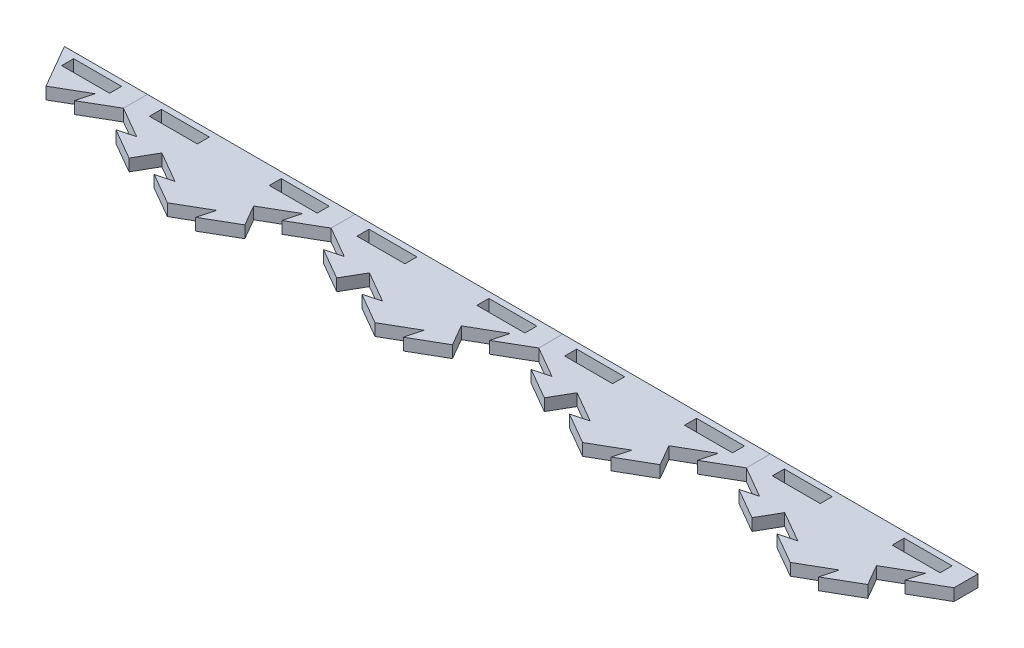
SolidWorks part; units mm, degrees
material "Cedar"
ref_plane "Front Plane" through (0, 0, 0) normal (0, 0, 1) x (1, 0, 0)
ref_plane "Top Plane" through (0, 0, 0) normal (0, 1, 0) x (1, 0, 0)
ref_plane "Right Plane" through (0, 0, 0) normal (1, 0, 0) x (0, 0, -1)
sketch "Sketch1" plane through (0, 0, 0) normal (0, 1, 0) x (1, 0, 0)
  line L0 (-54.9926, 0) -> (54.9926, 0) construction
  line L1 (-54.9926, 0) -> (0, -31.75)
  line L2 (0, -31.75) -> (54.9926, 0)
  line L3 (54.9926, 0) -> (54.9926, 63.5)
  line L4 (54.9926, 63.5) -> (0, 95.25)
  line L5 (0, 95.25) -> (-54.9926, 63.5)
  line L6 (-54.9926, 63.5) -> (-54.9926, 0)
  line L7 (0, -31.75) -> (0, 31.75) construction
  circle A0 centre (0, 31.75) radius 54.9926 construction
  point P9 (0, 0)
  dimension "D1" = 63.5
extrude "Boss-Extrude1" add sketch "Sketch1" against normal blind 6.35
sketch "Sketch2" plane through (0, 0, 0) normal (0, 1, 0) x (1, 0, 0)
  line L0 (-54.9926, 31.75) -> (54.9926, 31.75) construction
  line L1 (-54.9926, 63.5) -> (-54.9926, 0) construction
  line L2 (54.9926, 0) -> (54.9926, 63.5) construction
  point P2 (0, 31.75)
ref_axis "Axis1" through (0, 0, -31.75) along (0, 1, 0)
sketch "Sketch10" plane through (0, 0, 0) normal (0, 1, 0) x (1, 0, 0)
  line L0 (0, -31.75) -> (-16.4978, -22.225) construction
  line L1 (-16.4978, -22.225) -> (-7.8235, -19.9007)
  line L2 (-7.8235, -19.9007) -> (-24.3213, -10.3757)
  line L3 (-24.3213, -10.3757) -> (-27.4963, -15.875)
  line L4 (-16.4978, -22.225) -> (-27.4963, -15.875)
  line L5 (-54.9926, 0) -> (0, -31.75) construction
  dimension "D1" = 45
  dimension "D2" = 6.35
extrude "Cut-Extrude4" cut sketch "Sketch10" against normal through all
sketch "Sketch11" plane through (0, 0, 0) normal (0, 1, 0) x (1, 0, 0)
  line L0 (-27.4963, -15.875) -> (-54.9926, 0) construction
  line L1 (-27.4963, -15.875) -> (-30.6713, -21.3743)
  line L2 (-30.6713, -21.3743) -> (-47.1691, -11.8493)
  line L3 (-47.1691, -11.8493) -> (-38.4948, -9.525)
  line L4 (-38.4948, -9.525) -> (-27.4963, -15.875)
  line L5 (-38.4948, -9.525) -> (-54.9926, 0) construction
  line L6 (-38.4948, -9.525) -> (-54.9926, 0) construction
  line L7 (-54.9926, 0) -> (-27.4963, -15.875) construction
  line L8 (-54.9926, 63.5) -> (-54.9926, 0) construction
  dimension "D1" = 45
  dimension "D2" = 6.35
extrude "Boss-Extrude4" add sketch "Sketch11" against normal blind 6.35
pattern_circular "CirPattern1" count 2 every 60 about axis through (0, 0, -31.75) along (0, 1, 0) of "Cut-Extrude4", "Boss-Extrude4"
sketch "Sketch12" plane through (0, 0, 0) normal (0, 1, 0) x (1, 0, 0)
  line L0 (-54.9926, 12.7) -> (54.9926, 12.7)
  line L1 (-54.9926, 63.5) -> (-54.9926, 0) construction
  line L2 (54.9926, 0) -> (54.9926, 63.5) construction
  line L3 (54.9926, 12.7) -> (54.9926, 95.25)
  line L4 (54.9926, 95.25) -> (-54.9926, 95.25)
  line L5 (-54.9926, 95.25) -> (-54.9926, 12.7)
  line L6 (0, 0) -> (0, 12.7) construction
  dimension "D1" = 12.7
extrude "Cut-Extrude5" cut sketch "Sketch12" against normal through all
sketch "Sketch13" plane through (0, 0, 0) normal (0, 1, 0) x (1, 0, 0)
  line L0 (0, 0) -> (0, 12.7) construction
  line L1 (-54.9926, 12.7) -> (54.9926, 12.7) construction
  line L2 (-31.75, 6.35) -> (31.75, 6.35) construction
  line L4 (-44.45, 9.525) -> (-19.05, 9.525)
  line L5 (-44.45, 9.525) -> (-44.45, 3.175)
  line L6 (-44.45, 3.175) -> (-19.05, 3.175)
  line L7 (-19.05, 9.525) -> (-19.05, 3.175)
  line L8 (-44.45, 9.525) -> (-19.05, 3.175) construction
  line L9 (-44.45, 3.175) -> (-19.05, 9.525) construction
  line L10 (19.05, 9.525) -> (44.45, 9.525)
  line L11 (19.05, 9.525) -> (19.05, 3.175)
  line L12 (19.05, 3.175) -> (44.45, 3.175)
  line L13 (44.45, 9.525) -> (44.45, 3.175)
  line L14 (19.05, 9.525) -> (44.45, 3.175) construction
  line L15 (19.05, 3.175) -> (44.45, 9.525) construction
  point P7 (0, 6.35)
  point P8 (0, 6.35)
  dimension "D1" = 6.35
  dimension "D2" = 25.4
  dimension "D3" = 6.35
  dimension "D4" = 25.4
  dimension "D5" = 63.5
extrude "Cut-Extrude6" cut sketch "Sketch13" against normal through all
pattern_linear "LPattern1" count 5 spacing 109.9852 along (1, 0, 0) count 2 spacing 109.9852 along (-1, 0, 0) pattern seed only yes of bodies 136 131
sketch "Sketch14" plane through (0, 0, 0) normal (0, 1, 0) x (1, 0, 0)
  line L0 (439.9409, -31.75) -> (439.9409, 12.7)
  line L1 (384.9483, 12.7) -> (494.9335, 12.7) construction
  line L2 (439.9409, 12.7) -> (494.9335, 12.7)
  line L3 (494.9335, 12.7) -> (494.9335, -31.75)
  line L4 (494.9335, -31.75) -> (439.9409, -31.75)
  line L5 (-109.9852, -31.75) -> (-109.9852, 12.7)
  line L6 (-164.9778, 12.7) -> (-54.9926, 12.7) construction
  line L7 (-109.9852, 12.7) -> (-164.9778, 12.7)
  line L8 (-164.9778, 12.7) -> (-164.9778, -31.75)
  line L9 (-164.9778, -31.75) -> (-109.9852, -31.75)
  line L10 (415.6196, -10.3757) -> (428.9424, 12.7)
  line L11 (428.9424, 12.7) -> (439.9409, 12.7)
  line L12 (415.6196, -10.3757) -> (409.2696, -21.3743)
  line L13 (409.2696, -21.3743) -> (439.9409, -31.75)
  line L14 (-79.3139, -21.3743) -> (-98.9867, 12.7)
  line L15 (-98.9867, 12.7) -> (-109.9852, 12.7)
  line L16 (-79.3139, -21.3743) -> (-95.8117, -30.8993)
  line L17 (-95.8117, -30.8993) -> (-109.9852, -31.75)
  line L18 (-85.6639, -10.3757) -> (-79.3139, -21.3743) construction
  line M5 (484.3909, 9.525) -> (484.3909, 3.175)
  line M6 (484.3909, 3.175) -> (458.9909, 3.175)
  line M7 (458.9909, 3.175) -> (458.9909, 9.525)
  line M8 (458.9909, 9.525) -> (484.3909, 9.525)
  line M13 (494.9335, 12.7) -> (384.9483, 12.7)
  line M19 (415.6196, -10.3757) -> (432.1174, -19.9007)
  line M20 (432.1174, -19.9007) -> (423.4431, -22.225)
  line M21 (423.4431, -22.225) -> (439.9409, -31.75)
  line M22 (439.9409, -31.75) -> (456.4387, -22.225)
  line M23 (456.4387, -22.225) -> (454.1144, -30.8993)
  line M24 (454.1144, -30.8993) -> (470.6122, -21.3743)
  line M25 (470.6122, -21.3743) -> (464.2622, -10.3757)
  line M26 (464.2622, -10.3757) -> (480.76, -0.8507)
  line M27 (480.76, -0.8507) -> (478.4357, -9.525)
  line M28 (478.4357, -9.525) -> (494.9335, 0)
  line M29 (494.9335, 0) -> (494.9335, 12.7)
extrude "Cut-Extrude7" cut sketch "Sketch14" against normal through all contours L17 L16 L14 L15 L5 | L10 L0 M19 M20 M21 M13 | L0 M22 M23 M24 M25 M26 M27 M28 M29 M13 M8 M5 M6 M7 | L8 L9 L5 L7 region at (431.3731, 0, 7.3494) region at (460.5225, 0, 5.1278) region at (-137.4815, 0, 9.525) region at (-98.715, 0, 11.4335)
sketch "Sketch15" plane through (0, 0, 0) normal (0, 1, 0) x (1, 0, 0)
  line L0 (384.9483, 12.7) -> (428.9424, 12.7)
  line L1 (428.9424, 12.7) -> (428.9424, -21.3743)
  line L2 (428.9424, -21.3743) -> (384.9483, -21.3743)
  line L3 (384.9483, -21.3743) -> (384.9483, 12.7)
extrude "Cut-Extrude8" cut sketch "Sketch15" against normal through all
